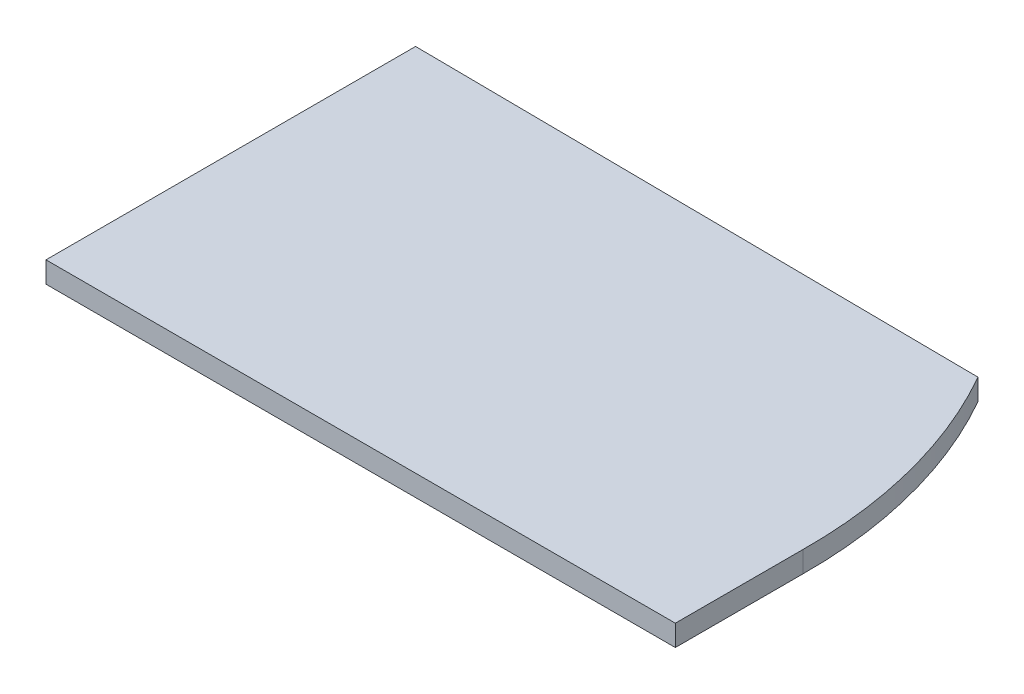
SolidWorks part; units mm, degrees
ref_plane "Front Plane" through (0, 0, 0) normal (0, 0, 1) x (1, 0, 0)
ref_plane "Top Plane" through (0, 0, 0) normal (0, 1, 0) x (1, 0, 0)
ref_plane "Right Plane" through (0, 0, 0) normal (1, 0, 0) x (0, 0, -1)
sketch "Sketch1" plane through (0, 0, 0) normal (0, 1, 0) x (1, 0, 0)
  line L0 (270.1932, 172.5395) -> (-10, 172.5395) construction
  line L1 (0, 0) -> (298, 0)
  line L2 (0, 0) -> (0, 175)
  line L4 (298, 0) -> (298, 60.4094)
  line L5 (0, 175) -> (268.7747, 172.5395)
  arc A0 (298, 60.4094) -> (268.7747, 172.5395) centre (75.7283, 62.3507) ccw
  arc A1 (296.7855, 84) -> (252.9805, 197) centre (68.28, 60.4094) ccw construction
  point P1 (298, 60.4094)
  point P8 (298, 59.988)
extrude "Boss-Extrude1" add sketch "Sketch1" along normal blind 10
